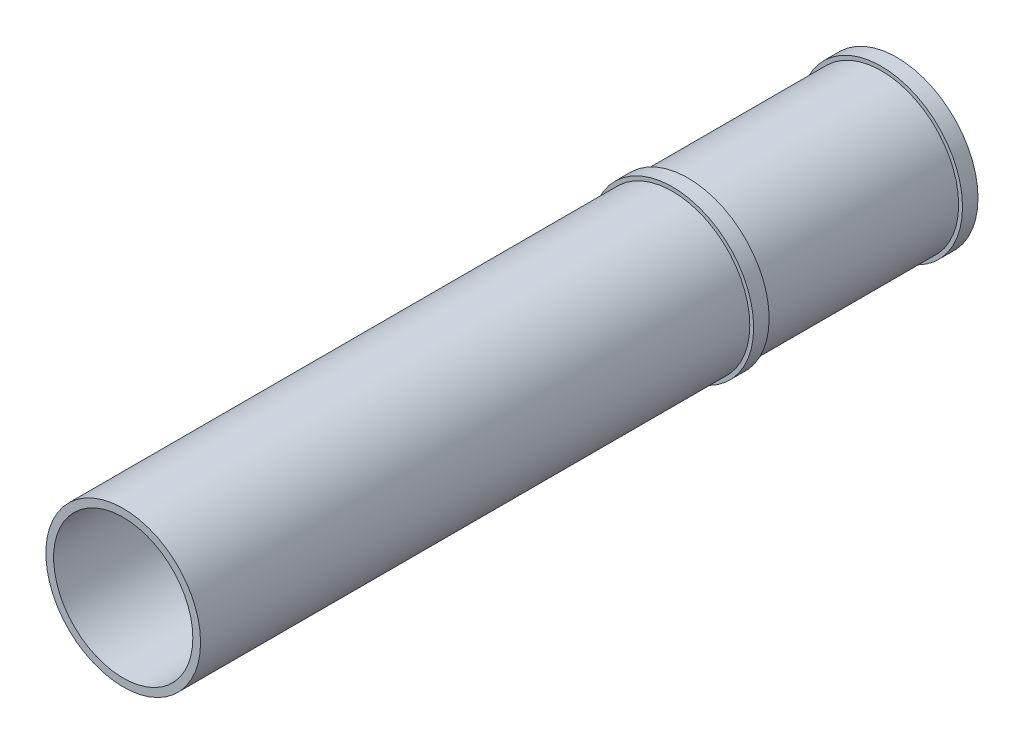
SolidWorks part; units mm, degrees
ref_plane "Front Plane" through (0, 0, 0) normal (0, 0, 1) x (1, 0, 0)
ref_plane "Top Plane" through (0, 0, 0) normal (0, 1, 0) x (1, 0, 0)
ref_plane "Right Plane" through (0, 0, 0) normal (1, 0, 0) x (0, 0, -1)
sketch "Sketch2" plane through (0, 0, 0) normal (0, 0, 1) x (1, 0, 0)
  circle A0 centre (0, 0) radius 20
  circle A1 centre (0, 0) radius 18
  circle A2 centre (0, 0) radius 21
  dimension "D1" = 40
  dimension "D2" = 2
  dimension "D3" = 1
extrude "Boss-Extrude1" add sketch "Sketch2" along normal blind 200 contours A0 A1 region at (-19.4343, 0, 0)
extrude "Boss-Extrude2" add sketch "Sketch2<3>" along normal blind 4 contours A2 A0 region at (-20.406, 0, 0)
sketch "Sketch2<3>" plane through (0, 0, 0) normal (0, 0, 1) x (1, 0, 0) same geometry as "Sketch2"
extrude "Boss-Extrude3" add sketch "Sketch2<4>" along normal blind 4 from offset 54 contours A2 A0 region at (-20.406, 0, 0)
sketch "Sketch2<4>" plane through (0, 0, 0) normal (0, 0, 1) x (1, 0, 0) same geometry as "Sketch2"
